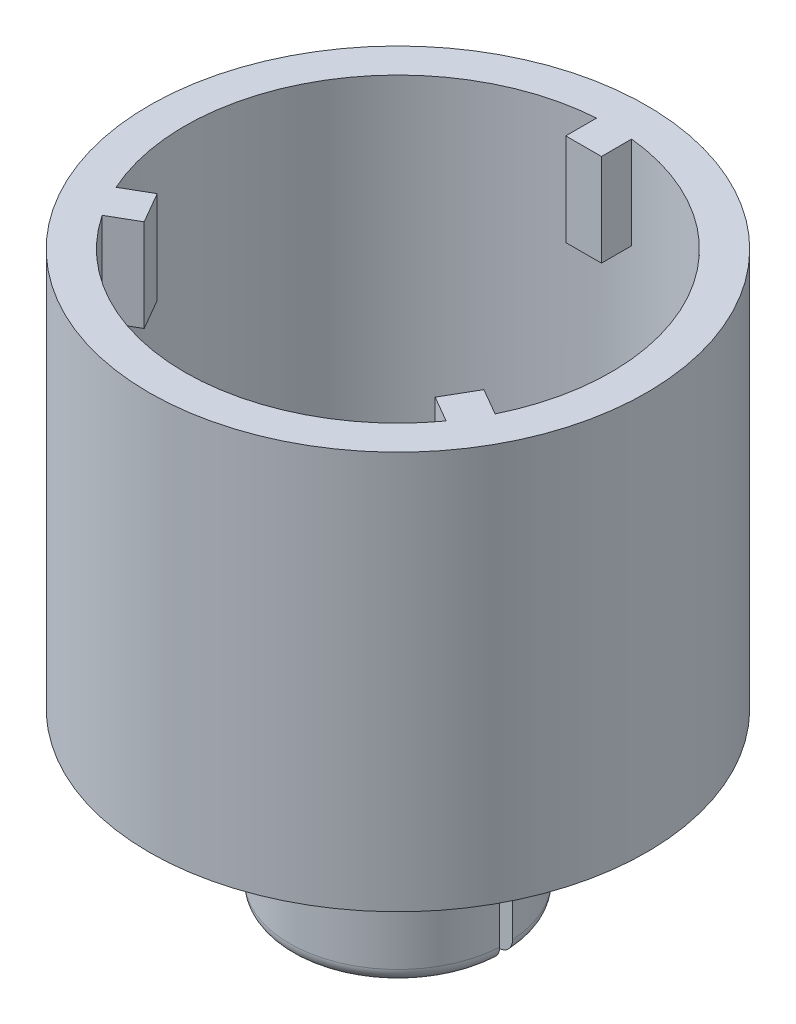
SolidWorks part; units mm, degrees
ref_plane "Front Plane" through (0, 0, 0) normal (0, 0, 1) x (1, 0, 0)
ref_plane "Top Plane" through (0, 0, 0) normal (0, 1, 0) x (1, 0, 0)
ref_plane "Right Plane" through (0, 0, 0) normal (1, 0, 0) x (0, 0, -1)
sketch "Sketch1" plane through (0, 0, 0) normal (0, 1, 0) x (1, 0, 0)
  circle A0 centre (0, 0) radius 35
  dimension "D1" = 70
extrude "Boss-Extrude1" add sketch "Sketch1" along normal blind 56
sketch "Sketch2" plane through (0, 56, 0) normal (0, 1, 0) x (1, 0, 0)
  circle A0 centre (0, 0) radius 30
  dimension "D1" = 60
extrude "Cut-Extrude1" cut sketch "Sketch2" against normal blind 46.9
sketch "Sketch3" plane through (0, 0, 0) normal (0, -1, 0) x (1, 0, 0)
  circle A0 centre (0, 0) radius 19.5
  dimension "D1" = 39
extrude "Boss-Extrude2" add sketch "Sketch3" along normal blind 7
sketch "Sketch4" plane through (0, -7, 0) normal (0, -1, 0) x (1, 0, 0)
  circle A0 centre (0, 0) radius 15.25
  dimension "D1" = 30.5
extrude "Boss-Extrude3" add sketch "Sketch4" along normal blind 16
fillet "Fillet1" radius 5 1 edges at (0, 0, -19.5)
sketch "Sketch5" plane through (0, 56, 0) normal (0, 1, 0) x (1, 0, 0)
  line L0 (-1.9905, 29.9339) -> (-1.9905, 25.6053)
  line L1 (-1.9905, 25.6053) -> (3.0302, 25.6053)
  line L2 (3.0302, 25.6053) -> (3.0302, 29.8466)
  line L3 (26.9188, -13.2431) -> (23.1701, -11.0788)
  line L4 (23.1701, -11.0788) -> (20.6597, -15.4269)
  line L5 (20.6597, -15.4269) -> (24.3328, -17.5475)
  line L6 (-24.9282, -16.6908) -> (-21.1796, -14.5265)
  line L7 (-21.1796, -14.5265) -> (-23.69, -10.1784)
  line L8 (-23.69, -10.1784) -> (-27.363, -12.299)
  circle A0 centre (0, 0) radius 30 construction
  arc A1 (24.3328, -17.5475) -> (26.9188, -13.2431) centre (0, 0) ccw
  circle A2 centre (0, 0) radius 30
  arc A3 (3.0302, 29.8466) -> (-1.9905, 29.9339) centre (0, 0) ccw
  arc A4 (-27.363, -12.299) -> (-24.9282, -16.6908) centre (0, 0) ccw
  point P19 (0, 0)
  dimension "D1" = 0
  dimension "D2" = 3
extrude "Boss-Extrude4" add sketch "Sketch5" against normal blind 13
sketch "Sketch7" plane through (0, -23, 0) normal (0, -1, 0) x (1, 0, 0)
  line L1 (33.0968, 0.9034) -> (-33.0968, 0.9034)
  line L2 (33.0968, 0.9034) -> (33.0968, -0.9034)
  line L3 (33.0968, -0.9034) -> (-33.0968, -0.9034)
  line L4 (-33.0968, 0.9034) -> (-33.0968, -0.9034)
  line L5 (33.0968, 0.9034) -> (-33.0968, -0.9034) construction
  line L6 (33.0968, -0.9034) -> (-33.0968, 0.9034) construction
  point P0 (0, 0)
extrude "Cut-Extrude2" cut sketch "Sketch7" against normal up to surface (16 mm away) up to face at (0, -7, -15.25)
fillet "Fillet2" radius 2 2 edges at (0, -23, 15.25) (0, -23, -15.25)
sketch "Sketch8" plane through (0, 9.1, 0) normal (0, 1, 0) x (1, 0, 0)
  circle A0 centre (0, 0) radius 10.3601
